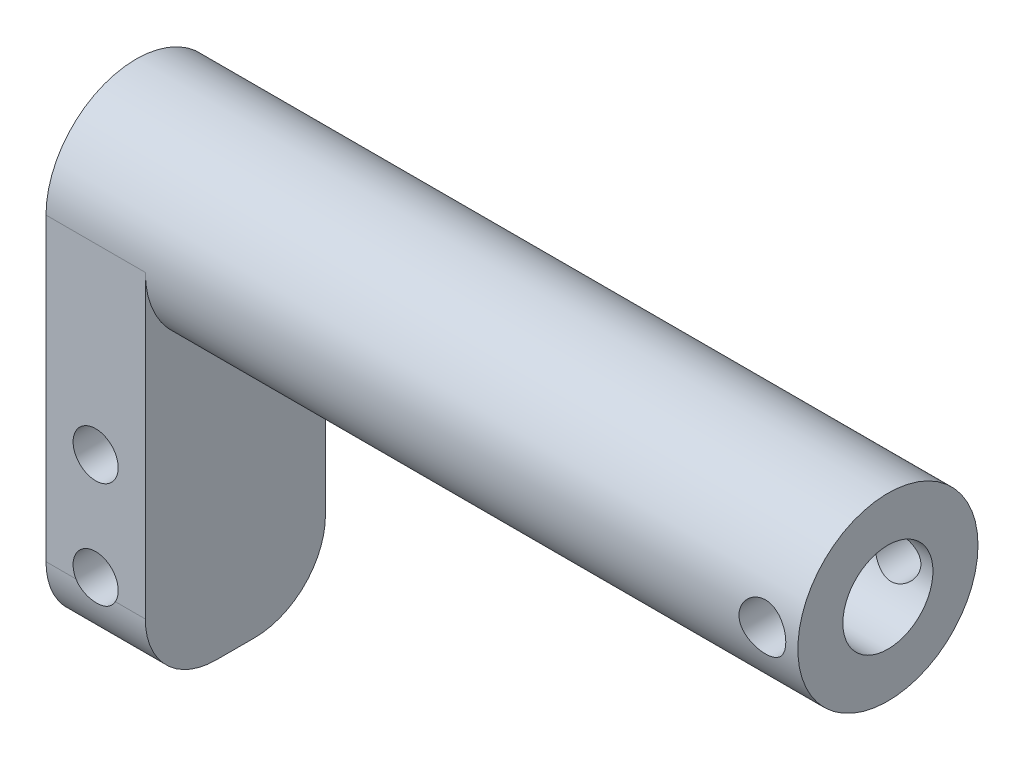
SolidWorks part; units mm, degrees
material "ABS"
ref_plane "Front Plane" through (0, 0, 0) normal (1, 0, 0) x (0, 1, 0)
ref_plane "Top Plane" through (0, 0, 0) normal (0, 0, 1) x (0, 1, 0)
ref_plane "Right Plane" through (0, 0, 0) normal (0, 1, 0) x (-1, 0, 0)
sketch "Sketch1" plane through (0, 0, 0) normal (1, 0, 0) x (0, 1, 0)
  circle A0 centre (0, 0) radius 3.175
  circle A1 centre (0, 0) radius 3
  circle A2 centre (0, 0) radius 6.35
  dimension "D1" = 6
  dimension "D2" = 6.35
  dimension "D3" = 12.7
extrude "Boss-Extrude1" add sketch "Sketch1" along normal blind 53 contours A2 A0 region at (0, -6.1704, 0)
extrude "Boss-Extrude2" add sketch "Sketch1<3>" along normal blind 7 contours A0 A1 region at (0, -3.0852, 0)
sketch "Sketch1<3>" plane through (0, 0, 0) normal (1, 0, 0) x (0, 1, 0) same geometry as "Sketch1"
ref_plane "Plane1" through (0, 0, 6.35) normal (0, 0, 1) x (0, 1, 0)
sketch "Sketch7" plane through (0, 0, 6.35) normal (0, 0, 1) x (0, 1, 0)
  line L2 (-6.35, -53) -> (6.35, -53) construction
  circle A0 centre (0, -50.5) radius 1.0922
  point P0 (0, -50.5)
  dimension "D2" = 2.1844
  dimension "D1" = 2.5
hole_wizard "M4x0.7 Tapped Hole1" positions "Sketch7" profile "Sketch9" tap size "M4x0.7" standard "ANSI Metric" end condition through all
sketch "Sketch9" plane through (50.5, 0, 6.35) normal (1, 0, 0) x (0, -1, 0)
  line L0 (0, 0) -> (0, 12.7)
  line L1 (0, 12.7) -> (1.65, 12.7)
  line L2 (1.65, 12.7) -> (1.65, 0)
  line L5 (1.65, 0) -> (0, 0)
  line L11 (0, -6.35) -> (0, 107.95) construction
  dimension "Thru Tap Drill Dia." = 3.3
  dimension "Thru Tap Drill Depth" = 12.7
cosmetic thread "Hole Thread10" parameters "D2"=4
sketch "Sketch10" plane through (0, 0, 0) normal (-1, 0, 0) x (0, -1, 0)
  line L0 (0, 6.35) -> (26.16, 6.35)
  line L1 (17.8805, 6.35) -> (-17.8805, 6.35) construction
  line L2 (26.16, 6.35) -> (26.16, -6.35)
  line L3 (26.16, -6.35) -> (0, -6.35)
  circle A0 centre (0, 0) radius 6.35 construction
  arc A1 (-1.65, -6.1319) -> (1.65, -6.1319) centre (0, 0) ccw construction
  arc A2 (0, 6.35) -> (0, -6.35) centre (0, 0) cw
  dimension "D1" = 26.16
extrude "Boss-Extrude3" add sketch "Sketch10" against normal blind 7 contours L0 A2 L3 L2 region at (0, -15.5262, 0)
fillet "Fillet2" radius 5 2 edges at (3.5, -26.16, 6.35) (3.5, -26.16, -6.35)
sketch "Sketch11" plane through (0, 0, -6.35) normal (0, 0, -1) x (1, 0, 0)
  line L0 (0, 0) -> (53, 0) construction
  line L1 (53, -6.35) -> (53, 6.35) construction
  line L2 (3.5, 21.16) -> (3.5, 0) construction
  line L3 (7, 21.16) -> (0, 21.16) construction
  circle A0 centre (3.5, 20.38) radius 1.59
  circle A1 centre (3.5, 12.88) radius 1.59
  dimension "D3" = 3.18
  dimension "D4" = 3.18
  dimension "D1" = 12.88
  dimension "D2" = 7.5
extrude "Cut-Extrude5" cut sketch "Sketch11" against normal through all
sketch "Sketch14" plane through (0, 0, 0) normal (-1, 0, 0) x (0, 0, 1)
  line L0 (0.5112, -3.2591) -> (0.3942, -3.8443)
  line L1 (0, 0) -> (0, -3.9) construction
  line L2 (0, 0) -> (0.5602, -3.2689) construction
  line L3 (0.6032, -3.2433) -> (0.9083, -3.7562)
  line L4 (-0.6343, -3.2373) -> (-0.9444, -3.7473)
  line L5 (-0.5425, -3.254) -> (-0.4312, -3.8403)
  line L6 (-1.7033, -2.8251) -> (-2.1691, -3.1983)
  line L7 (-1.6227, -2.8722) -> (-1.7186, -3.4613)
  line L8 (-2.5669, -2.0722) -> (-3.1322, -2.2635)
  line L9 (-2.5072, -2.144) -> (-2.7988, -2.6647)
  line L10 (-3.1208, -1.0693) -> (-3.7174, -1.0558)
  line L11 (-3.0893, -1.1572) -> (-3.5414, -1.5468)
  line L12 (-3.2983, 0.0625) -> (-3.8543, 0.2793)
  line L13 (-3.2988, -0.0308) -> (-3.8569, -0.2422)
  line L14 (-3.078, 1.1869) -> (-3.5264, 1.5808)
  line L15 (-3.1104, 1.0993) -> (-3.7071, 1.0915)
  line L16 (-2.4865, 2.168) -> (-2.773, 2.6915)
  line L17 (-2.5468, 2.0968) -> (-3.1102, 2.2936)
  line L18 (-1.595, 2.8877) -> (-1.6852, 3.4776)
  line L19 (-1.6761, 2.8414) -> (-2.1382, 3.219)
  line L20 (-0.5112, 3.2591) -> (-0.3942, 3.8443)
  line L21 (-0.6032, 3.2433) -> (-0.9083, 3.7562)
  line L22 (0.6343, 3.2373) -> (0.9444, 3.7473)
  line L23 (0.5425, 3.254) -> (0.4312, 3.8403)
  line L24 (1.7033, 2.8251) -> (2.1691, 3.1983)
  line L25 (1.6227, 2.8722) -> (1.7186, 3.4613)
  line L26 (2.5669, 2.0722) -> (3.1322, 2.2635)
  line L27 (2.5072, 2.144) -> (2.7988, 2.6647)
  line L28 (3.1208, 1.0693) -> (3.7174, 1.0558)
  line L29 (3.0893, 1.1572) -> (3.5414, 1.5468)
  line L30 (3.2983, -0.0625) -> (3.8543, -0.2793)
  line L31 (3.2988, 0.0308) -> (3.8569, 0.2422)
  line L32 (3.078, -1.1869) -> (3.5264, -1.5808)
  line L33 (3.1104, -1.0993) -> (3.7071, -1.0915)
  line L34 (2.4865, -2.168) -> (2.773, -2.6915)
  line L35 (2.5468, -2.0968) -> (3.1102, -2.2936)
  line L36 (1.595, -2.8877) -> (1.6852, -3.4776)
  line L37 (1.6761, -2.8414) -> (2.1382, -3.219)
  line L38 (-0.0375, -3.8998) -> (0, -3.9)
  line L39 (-1.3691, -3.6518) -> (-1.3339, -3.6648)
  line L40 (-2.5355, -2.9633) -> (-2.5069, -2.9876)
  line L41 (-3.3775, -1.95) -> (-3.3961, -1.9174)
  line L42 (-3.8408, -0.6772) -> (-3.8471, -0.6402)
  line L43 (-3.8408, 0.6772) -> (-3.8341, 0.7142)
  line L44 (-3.3775, 1.95) -> (-3.3586, 1.9824)
  line L45 (-2.5069, 2.9876) -> (-2.478, 3.0116)
  line L46 (-1.3339, 3.6648) -> (-1.2985, 3.6775)
  line L47 (0, 3.9) -> (0.0375, 3.8998)
  line L48 (1.3339, 3.6648) -> (1.3691, 3.6518)
  line L49 (2.5069, 2.9876) -> (2.5355, 2.9633)
  line L50 (3.3775, 1.95) -> (3.3961, 1.9174)
  line L51 (3.8408, 0.6772) -> (3.8471, 0.6402)
  line L52 (3.8408, -0.6772) -> (3.8341, -0.7142)
  line L53 (3.3775, -1.95) -> (3.3586, -1.9824)
  line L54 (2.5069, -2.9876) -> (2.478, -3.0116)
  line L55 (1.3339, -3.6648) -> (1.2985, -3.6775)
  arc A0 (0.3496, -3.8843) -> (0, -3.9) centre (0, 0) cw
  arc A1 (0.3496, -3.8843) -> (0.3942, -3.8443) centre (0.3452, -3.8345) ccw
  arc A2 (0.5112, -3.2591) -> (0.6032, -3.2433) centre (0.5602, -3.2689) cw
  arc A3 (0.4199, -3.8983) -> (0.3942, -3.8443) centre (0.4432, -3.8541) cw
  arc A4 (0.4199, -3.8983) -> (0.7367, -4.0472) centre (2.2357, -0.4468) ccw
  arc A6 (0.9636, -3.7791) -> (0.9083, -3.7562) centre (0.9513, -3.7306) cw
  arc A7 (0.9636, -3.7791) -> (1.2985, -3.6775) centre (0, 0) ccw
  arc A8 (-0.9999, -3.7696) -> (-1.3339, -3.6648) centre (0, 0) cw
  arc A9 (-0.9999, -3.7696) -> (-0.9444, -3.7473) centre (-0.9871, -3.7213) ccw
  arc A10 (-0.6343, -3.2373) -> (-0.5425, -3.254) centre (-0.5916, -3.2633) cw
  arc A11 (-0.387, -3.8808) -> (-0.4312, -3.8403) centre (-0.3821, -3.831) cw
  arc A12 (-0.387, -3.8808) -> (-0.0375, -3.8998) centre (0, 0) ccw
  arc A13 (-2.2289, -3.2003) -> (-2.5069, -2.9876) centre (0, 0) cw
  arc A14 (-2.2289, -3.2003) -> (-2.1691, -3.1983) centre (-2.2004, -3.1593) ccw
  arc A15 (-1.7033, -2.8251) -> (-1.6227, -2.8722) centre (-1.6721, -2.8642) cw
  arc A16 (-1.691, -3.5143) -> (-1.7186, -3.4613) centre (-1.6693, -3.4693) cw
  arc A17 (-1.691, -3.5143) -> (-1.3691, -3.6518) centre (0, 0) ccw
  arc A18 (-3.1891, -2.245) -> (-3.3775, -1.95) centre (0, 0) cw
  arc A19 (-3.1891, -2.245) -> (-3.1322, -2.2635) centre (-3.1482, -2.2162) ccw
  arc A20 (-2.5669, -2.0722) -> (-2.5072, -2.144) centre (-2.5508, -2.1196) cw
  arc A21 (-2.791, -2.7241) -> (-2.7988, -2.6647) centre (-2.7552, -2.6891) cw
  arc A22 (-2.791, -2.7241) -> (-2.5355, -2.9633) centre (0, 0) ccw
  arc A23 (-3.7646, -1.0188) -> (-3.8408, -0.6772) centre (0, 0) cw
  arc A24 (-3.7646, -1.0188) -> (-3.7174, -1.0558) centre (-3.7163, -1.0058) ccw
  arc A25 (-3.1208, -1.0693) -> (-3.0893, -1.1572) centre (-3.1219, -1.1193) cw
  arc A26 (-3.5543, -1.6052) -> (-3.5414, -1.5468) centre (-3.5088, -1.5846) cw
  arc A27 (-3.5543, -1.6052) -> (-3.3961, -1.9174) centre (0, 0) ccw
  arc A28 (-3.886, 0.3302) -> (-3.8408, 0.6772) centre (0, 0) cw
  arc A29 (-3.886, 0.3302) -> (-3.8543, 0.2793) centre (-3.8362, 0.3259) ccw
  arc A30 (-3.2983, 0.0625) -> (-3.2988, -0.0308) centre (-3.3165, 0.016) cw
  arc A31 (-3.889, -0.2928) -> (-3.8569, -0.2422) centre (-3.8391, -0.289) cw
  arc A32 (-3.889, -0.2928) -> (-3.8471, -0.6402) centre (0, 0) ccw
  arc A33 (-3.5387, 1.6393) -> (-3.3775, 1.95) centre (0, 0) cw
  arc A34 (-3.5387, 1.6393) -> (-3.5264, 1.5808) centre (-3.4934, 1.6183) ccw
  arc A35 (-3.078, 1.1869) -> (-3.1104, 1.0993) centre (-3.111, 1.1493) cw
  arc A36 (-3.7546, 1.055) -> (-3.7071, 1.0915) centre (-3.7065, 1.0415) cw
  arc A37 (-3.7546, 1.055) -> (-3.8341, 0.7142) centre (0, 0) ccw
  arc A38 (-2.7646, 2.7508) -> (-2.5069, 2.9876) centre (0, 0) cw
  arc A39 (-2.7646, 2.7508) -> (-2.773, 2.6915) centre (-2.7292, 2.7155) ccw
  arc A40 (-2.4865, 2.168) -> (-2.5468, 2.0968) centre (-2.5303, 2.144) cw
  arc A41 (-3.1673, 2.2755) -> (-3.1102, 2.2936) centre (-3.1267, 2.2464) cw
  arc A42 (-3.1673, 2.2755) -> (-3.3586, 1.9824) centre (0, 0) ccw
  arc A43 (-1.6571, 3.5305) -> (-1.3339, 3.6648) centre (0, 0) cw
  arc A44 (-1.6571, 3.5305) -> (-1.6852, 3.4776) centre (-1.6358, 3.4852) ccw
  arc A45 (-1.595, 2.8877) -> (-1.6761, 2.8414) centre (-1.6444, 2.8801) cw
  arc A46 (-2.198, 3.2216) -> (-2.1382, 3.219) centre (-2.1698, 3.1803) cw
  arc A47 (-2.198, 3.2216) -> (-2.478, 3.0116) centre (0, 0) ccw
  arc A48 (-0.3496, 3.8843) -> (0, 3.9) centre (0, 0) cw
  arc A49 (-0.3496, 3.8843) -> (-0.3942, 3.8443) centre (-0.3452, 3.8345) ccw
  arc A50 (-0.5112, 3.2591) -> (-0.6032, 3.2433) centre (-0.5602, 3.2689) cw
  arc A51 (-0.9636, 3.7791) -> (-0.9083, 3.7562) centre (-0.9513, 3.7306) cw
  arc A52 (-0.9636, 3.7791) -> (-1.2985, 3.6775) centre (0, 0) ccw
  arc A53 (0.9999, 3.7696) -> (1.3339, 3.6648) centre (0, 0) cw
  arc A54 (0.9999, 3.7696) -> (0.9444, 3.7473) centre (0.9871, 3.7213) ccw
  arc A55 (0.6343, 3.2373) -> (0.5425, 3.254) centre (0.5916, 3.2633) cw
  arc A56 (0.387, 3.8808) -> (0.4312, 3.8403) centre (0.3821, 3.831) cw
  arc A57 (0.387, 3.8808) -> (0.0375, 3.8998) centre (0, 0) ccw
  arc A58 (2.2289, 3.2003) -> (2.5069, 2.9876) centre (0, 0) cw
  arc A59 (2.2289, 3.2003) -> (2.1691, 3.1983) centre (2.2004, 3.1593) ccw
  arc A60 (1.7033, 2.8251) -> (1.6227, 2.8722) centre (1.6721, 2.8642) cw
  arc A61 (1.691, 3.5143) -> (1.7186, 3.4613) centre (1.6693, 3.4693) cw
  arc A62 (1.691, 3.5143) -> (1.3691, 3.6518) centre (0, 0) ccw
  arc A63 (3.1891, 2.245) -> (3.3775, 1.95) centre (0, 0) cw
  arc A64 (3.1891, 2.245) -> (3.1322, 2.2635) centre (3.1482, 2.2162) ccw
  arc A65 (2.5669, 2.0722) -> (2.5072, 2.144) centre (2.5508, 2.1196) cw
  arc A66 (2.791, 2.7241) -> (2.7988, 2.6647) centre (2.7552, 2.6891) cw
  arc A67 (2.791, 2.7241) -> (2.5355, 2.9633) centre (0, 0) ccw
  arc A68 (3.7646, 1.0188) -> (3.8408, 0.6772) centre (0, 0) cw
  arc A69 (3.7646, 1.0188) -> (3.7174, 1.0558) centre (3.7163, 1.0058) ccw
  arc A70 (3.1208, 1.0693) -> (3.0893, 1.1572) centre (3.1219, 1.1193) cw
  arc A71 (3.5543, 1.6052) -> (3.5414, 1.5468) centre (3.5088, 1.5846) cw
  arc A72 (3.5543, 1.6052) -> (3.3961, 1.9174) centre (0, 0) ccw
  arc A73 (3.886, -0.3302) -> (3.8408, -0.6772) centre (0, 0) cw
  arc A74 (3.886, -0.3302) -> (3.8543, -0.2793) centre (3.8362, -0.3259) ccw
  arc A75 (3.2983, -0.0625) -> (3.2988, 0.0308) centre (3.3165, -0.016) cw
  arc A76 (3.889, 0.2928) -> (3.8569, 0.2422) centre (3.8391, 0.289) cw
  arc A77 (3.889, 0.2928) -> (3.8471, 0.6402) centre (0, 0) ccw
  arc A78 (3.5387, -1.6393) -> (3.3775, -1.95) centre (0, 0) cw
  arc A79 (3.5387, -1.6393) -> (3.5264, -1.5808) centre (3.4934, -1.6183) ccw
  arc A80 (3.078, -1.1869) -> (3.1104, -1.0993) centre (3.111, -1.1493) cw
  arc A81 (3.7546, -1.055) -> (3.7071, -1.0915) centre (3.7065, -1.0415) cw
  arc A82 (3.7546, -1.055) -> (3.8341, -0.7142) centre (0, 0) ccw
  arc A83 (2.7646, -2.7508) -> (2.5069, -2.9876) centre (0, 0) cw
  arc A84 (2.7646, -2.7508) -> (2.773, -2.6915) centre (2.7292, -2.7155) ccw
  arc A85 (2.4865, -2.168) -> (2.5468, -2.0968) centre (2.5303, -2.144) cw
  arc A86 (3.1673, -2.2755) -> (3.1102, -2.2936) centre (3.1267, -2.2464) cw
  arc A87 (3.1673, -2.2755) -> (3.3586, -1.9824) centre (0, 0) ccw
  arc A88 (1.6571, -3.5305) -> (1.3339, -3.6648) centre (0, 0) cw
  arc A89 (1.6571, -3.5305) -> (1.6852, -3.4776) centre (1.6358, -3.4852) ccw
  arc A90 (1.595, -2.8877) -> (1.6761, -2.8414) centre (1.6444, -2.8801) cw
  arc A91 (2.198, -3.2216) -> (2.1382, -3.219) centre (2.1698, -3.1803) cw
  arc A92 (2.198, -3.2216) -> (2.478, -3.0116) centre (0, 0) ccw
  point P207 (0, 0)
  dimension "D1" = 3.9
  dimension "D2" = 0.05
  dimension "D3" = 0.05
  dimension "D4" = 0.04
  dimension "D5" = 18
  dimension "D6" = 0.5968
  dimension "D8" = 0.35
extrude "Cut-Extrude6" cut sketch "Sketch14" against normal blind 15 contours A91 A92 L54 A83 A84 L34 A85 L35 A86 A87 L53 A78 A79 L32 A80 L33 A81 A82 L52 A73 A74 L30 A75 L31 A76 A77 L51 A68 A69 L28 A70 L29 A71 A72 L50 A63 A64 L26 A65 L27 A66 A67 L49 A58 A59 L24 A60 L25 A61 A62 L48 region at (0, 0, 0)
